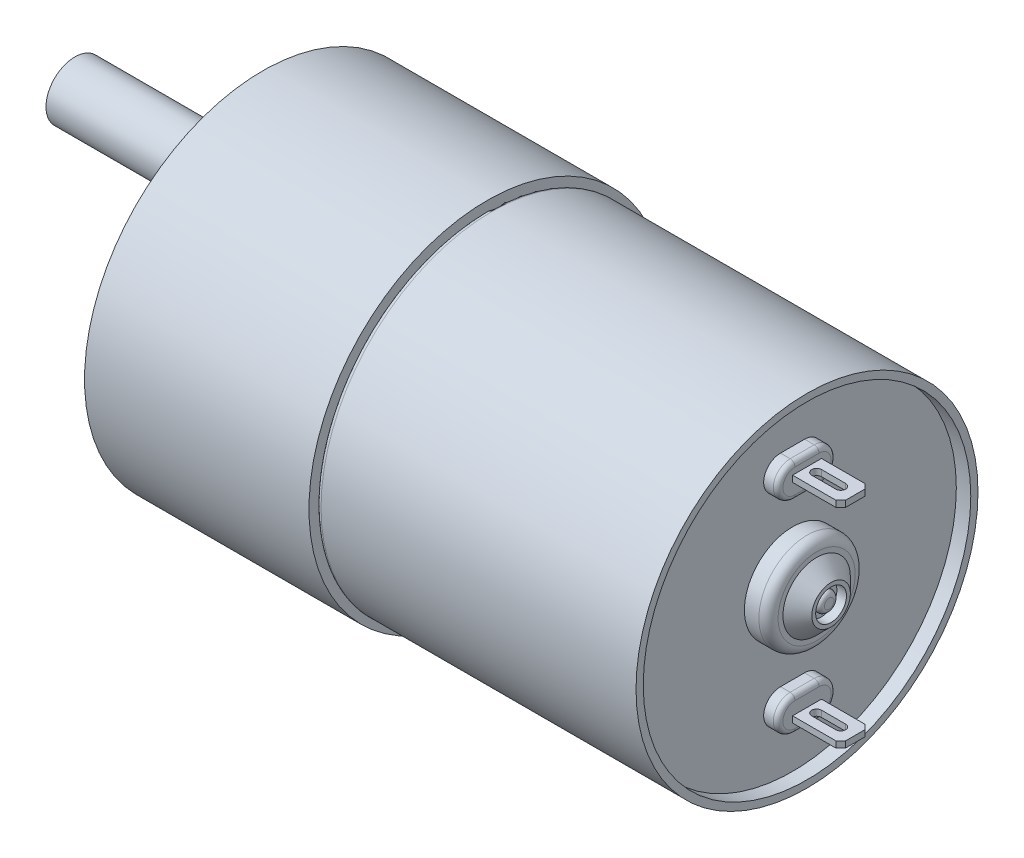
SolidWorks part; units mm, degrees
ref_plane "Ön Düzlem" through (0, 0, 0) normal (0, 0, 1) x (1, 0, 0)
ref_plane "Üst Düzlem" through (0, 0, 0) normal (0, 1, 0) x (1, 0, 0)
ref_plane "Sağ Düzlem" through (0, 0, 0) normal (1, 0, 0) x (0, 0, -1)
sketch "Çizim1" plane through (0, 0, 0) normal (1, 0, 0) x (0, 0, -1)
  circle A0 centre (0, 0) radius 18.5
extrude "Yükseklik-Ekstrüzyon1" add sketch "Çizim1" along normal blind 23.3
sketch "Çizim2" plane through (0, 0, 0) normal (-1, 0, 0) x (0, 0, 1)
  circle A0 centre (0, 0) radius 11.5
  circle A1 centre (0, 0) radius 18.5 construction
  dimension "D1" = 7
extrude "Kes-Ekstrüzyon1" cut sketch "Çizim2" against normal blind 0.5 draft 15
sketch "Çizim3" plane through (0, 0, 0) normal (-1, 0, 0) x (0, 0, 1)
  circle A0 centre (-15, 0) radius 1.25
  circle A1 centre (0, 0) radius 18.5 construction
  circle A2 centre (-7.5, 12.9904) radius 1.25
  circle A3 centre (7.5, 12.9904) radius 1.25
  circle A4 centre (15, 0) radius 1.25
  circle A5 centre (7.5, -12.9904) radius 1.25
  circle A6 centre (-7.5, -12.9904) radius 1.25
  dimension "D1" = 15
  dimension "D3" = 15
  dimension "D2" = 6
extrude "Kes-Ekstrüzyon2" cut sketch "Çizim3" against normal blind 5
sketch "Çizim4" plane through (0.5, 0, 0) normal (-1, 0, 0) x (0, 0, 1)
  line L0 (-18.6371, 13) -> (18.5735, 13) construction
  circle A0 centre (0, 7) radius 6
  circle A1 centre (7.5, 12.9904) radius 1.25 construction
  circle A2 centre (0, 0) radius 18.5 construction
  dimension "D1" = 7.5
  dimension "D2" = 13
extrude "Yükseklik-Ekstrüzyon2" add sketch "Çizim4" along normal blind 5
fillet "Radyus1" radius 0.5 2 edges at (0.5, 1, 0) (0, 13, 0)
sketch "Çizim5" plane through (-4.5, 0, 0) normal (-1, 0, 0) x (0, 0, 1)
  circle A0 centre (0, 7) radius 3
extrude "Yükseklik-Ekstrüzyon3" add sketch "Çizim5" along normal blind 15
sketch "Çizim6" plane through (-19.5, 0, 0) normal (-1, 0, 0) x (0, 0, 1)
  line L1 (-2.836, 4.5) -> (2.2792, 4.5)
  line L2 (-2.836, 4.5) -> (-2.836, 2.8808)
  line L3 (-2.836, 2.8808) -> (2.2792, 2.8808)
  line L4 (2.2792, 4.5) -> (2.2792, 2.8808)
  circle A0 centre (0, 7) radius 3 construction
  dimension "D1" = 2.5
extrude "Kes-Ekstrüzyon3" cut sketch "Çizim6" against normal blind 14
sketch "Çizim7" plane through (23.3, 0, 0) normal (1, 0, 0) x (0, 0, -1)
  circle A0 centre (0, 0) radius 17.75
extrude "Yükseklik-Ekstrüzyon4" add sketch "Çizim7" along normal blind 33.2
sketch "Çizim8" plane through (0, 0, 0) normal (0, 1, 0) x (1, 0, 0)
  line L0 (23.3, 17.25) -> (23.3, 20.9309)
  line L2 (23.8, 20.9309) -> (23.3, 20.9309)
  line L3 (56.5, 0) -> (-24.198, 0) construction
  line L6 (56.5, 17.75) -> (23.3, 17.75) construction
  line L7 (23.8, 17.75) -> (23.8, 20.9309)
  line L8 (56.5, -17.75) -> (56.5, 17.75) construction
  arc A0 (23.8, 17.75) -> (23.3, 17.25) centre (23.8, 17.25) ccw
revolve "Kes-Döndür1" cut sketch "Çizim8" angle 360 about L3
sketch "Çizim9" plane through (56.5, 0, 0) normal (1, 0, 0) x (0, 0, -1)
  circle A0 centre (0, 0) radius 17
  circle A1 centre (0, 0) radius 17.75 construction
  dimension "D1" = 0.75
extrude "Kes-Ekstrüzyon4" cut sketch "Çizim9" against normal blind 1.5
sketch "Çizim10" plane through (55, 0, 0) normal (1, 0, 0) x (0, 0, -1)
  circle A0 centre (0, 0) radius 5
extrude "Yükseklik-Ekstrüzyon5" add sketch "Çizim10" along normal blind 2.5
fillet "Radyus3" radius 1 1 edges at (57.5, 0, -5)
sketch "Çizim11" plane through (57.5, 0, 0) normal (1, 0, 0) x (0, 0, -1)
  circle A0 centre (0, 0) radius 3.5
extrude "Yükseklik-Ekstrüzyon6" add sketch "Çizim11" along normal blind 1.5 draft 45
sketch "Çizim12" plane through (59, 0, 0) normal (1, 0, 0) x (0, 0, -1)
  circle A0 centre (0, 0) radius 1.6
  circle A1 centre (0, 0) radius 2 construction
  dimension "D1" = 0.4
extrude "Kes-Ekstrüzyon5" cut sketch "Çizim12" against normal blind 1
sketch "Çizim13" plane through (58, 0, 0) normal (1, 0, 0) x (0, 0, -1)
  circle A0 centre (0, 0) radius 1
extrude "Yükseklik-Ekstrüzyon7" add sketch "Çizim13" along normal blind 0.8
fillet "Radyus4" radius 0.5 1 edges at (58.8, 0, -1)
sketch "Çizim14" plane through (55, 0, 0) normal (1, 0, 0) x (0, 0, -1)
  line L1 (-1.25, 12.25) -> (1.25, 12.25)
  line L3 (-1.25, 8.75) -> (1.25, 8.75)
  circle A0 centre (0, 0) radius 17.75 construction
  arc A1 (1.25, 8.75) -> (1.25, 12.25) centre (1.25, 10.5) ccw
  arc A2 (-1.25, 12.25) -> (-1.25, 8.75) centre (-1.25, 10.5) ccw
  dimension "D3" = 3.5
  dimension "D4" = 12.25
extrude "Yükseklik-Ekstrüzyon8" add sketch "Çizim14" along normal blind 1.5
fillet "Radyus5" radius 0.5 4 edges at (56.5, 10.5, -3) (56.5, 12.25, 0) (56.5, 10.5, 3) (56.5, 8.75, 0)
sketch "Çizim15" plane through (56.5, 0, 0) normal (1, 0, 0) x (0, 0, -1)
  line L1 (-1.5, 11.142) -> (1.5, 11.142)
  line L2 (-1.5, 11.142) -> (-1.5, 10.492)
  line L3 (-1.5, 10.492) -> (1.5, 10.492)
  line L4 (1.5, 11.142) -> (1.5, 10.492)
  dimension "D1" = 3
  dimension "D2" = 0.65
  dimension "D3" = 1.5
extrude "Yükseklik-Ekstrüzyon9" add sketch "Çizim15" along normal blind 5
sketch "Çizim16" plane through (0, 11.142, 0) normal (0, 1, 0) x (1, 0, 0)
  line L0 (57.5, 0) -> (60, 0) construction
  line L1 (57.5, 0.512) -> (60, 0.512)
  line L2 (57.5, -0.512) -> (60, -0.512)
  line L3 (61.5, -1.5) -> (56.5, -1.5) construction
  line L4 (61.5, 1.5) -> (61.5, -1.5) construction
  arc A0 (57.5, 0.512) -> (57.5, -0.512) centre (57.5, 0) ccw
  arc A1 (60, -0.512) -> (60, 0.512) centre (60, 0) ccw
  point P2 (58.75, 0)
  dimension "D1" = 1.5
  dimension "D2" = 2.5
  dimension "D3" = 1.5
extrude "Kes-Ekstrüzyon6" cut sketch "Çizim16" against normal up to surface (0.65 mm away) up to face at (59, 10.492, 0)
chamfer "Pah1" distance 0.5 angle 45 2 edges at (61.5, 10.817, 1.5) (61.5, 10.817, -1.5)
mirror "Aynalama2" about plane through (0, 0, 0) normal (0, 1, 0) of "Pah1", "Kes-Ekstrüzyon6", "Yükseklik-Ekstrüzyon9", "Radyus5", "Yükseklik-Ekstrüzyon8"
